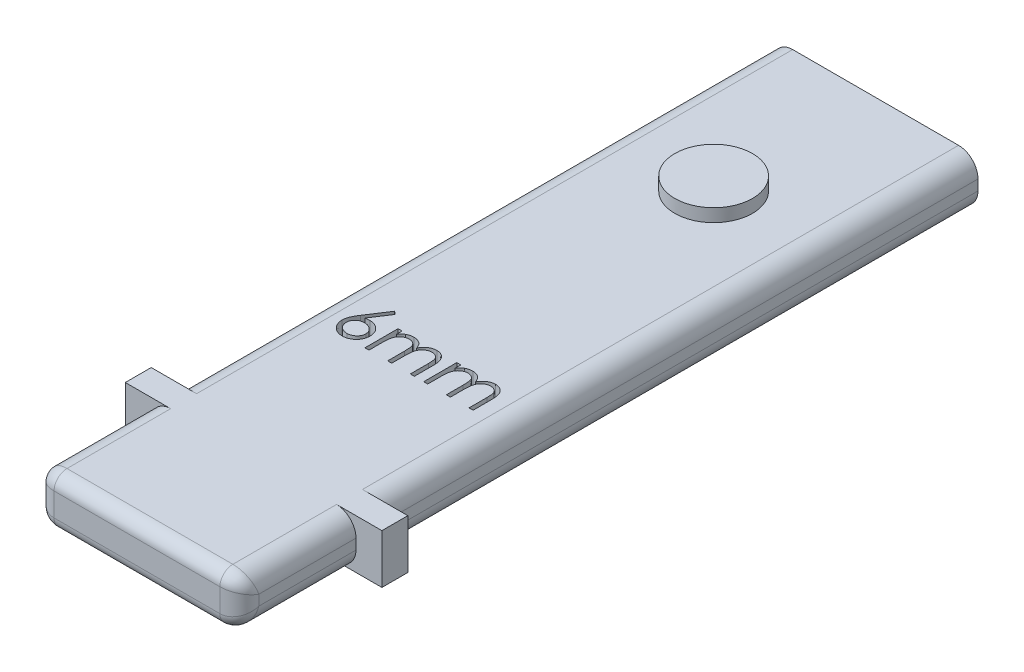
SolidWorks part; units mm, degrees
ref_plane "Front Plane" through (0, 0, 0) normal (0, 0, 1) x (1, 0, 0)
ref_plane "Top Plane" through (0, 0, 0) normal (0, 1, 0) x (1, 0, 0)
ref_plane "Right Plane" through (0, 0, 0) normal (1, 0, 0) x (0, 0, -1)
sketch "Sketch2" plane through (0, 0, 0) normal (0, 1, 0) x (1, 0, 0)
  line L1 (0, 0) -> (15.8, 0)
  line L2 (0, 0) -> (0, 57)
  line L3 (0, 57) -> (15.8, 57)
  line L4 (15.8, 0) -> (15.8, 57)
  dimension "D1" = 57
  dimension "D2" = 15.8
extrude "Boss-Extrude1" add sketch "Sketch2" along normal blind 3.8
fillet "Fillet3" radius 1 2 edges at (7.9, 0, 0) (7.9, 3.8, 0)
sketch "Sketch5" plane through (0, 3.8, 0) normal (0, 1, 0) x (1, 0, 0)
  line L0 (15.8, 57) -> (0, 57) construction
  circle A0 centre (7.9, 44.5) radius 3
  point P4 (7.9, 57)
  dimension "D1" = 6
  dimension "D2" = 12.5
extrude "Boss-Extrude4" add sketch "Sketch5" along normal blind 1
sketch "Sketch6" plane through (15.8, 0, 0) normal (1, 0, 0) x (0, 0, -1)
  line L0 (9, 3.8) -> (9, 0)
  line L1 (1, 3.8) -> (57, 3.8) construction
  line L2 (1, 0) -> (57, 0) construction
  line L3 (9, 0) -> (11, 0)
  line L4 (11, 0) -> (11, 3.8)
  line L5 (11, 3.8) -> (9, 3.8)
  line L6 (0, 2.8) -> (0, 1) construction
  dimension "D1" = 9
  dimension "D2" = 2
extrude "Boss-Extrude5" add sketch "Sketch6" along normal blind 2
sketch "Sketch7" plane through (0, 0, 0) normal (-1, 0, 0) x (0, 0, 1)
  line L0 (-57, 0) -> (-1, 0) construction
  line L1 (-9, 0) -> (-11, 0)
  line L2 (-9, 0) -> (-9, 3.8)
  line L3 (-9, 3.8) -> (-11, 3.8)
  line L4 (-11, 0) -> (-11, 3.8)
  line L5 (-57, 3.8) -> (-1, 3.8) construction
  line L6 (0, 2.8) -> (0, 1) construction
  dimension "D1" = 9
  dimension "D2" = 2
extrude "Boss-Extrude6" add sketch "Sketch7" along normal blind 2
fillet "Fillet4" radius 1.5 14 edges at (0, 0.2929, -0.2929) (0, 1.9, 0) (0, 3.5071, -0.2929) (15.8, 0.2929, -0.2929) (15.8, 1.9, 0) (15.8, 3.5071, -0.2929) (0, 0, -34) (0, 0, -5) (0, 3.8, -5) (0, 3.8, -34) (15.8, 0, -34) (15.8, 3.8, -34) (15.8, 0, -5) (15.8, 3.8, -5)
sketch "Sketch9" plane through (0, 3.8, 0) normal (0, 1, 0) x (1, 0, 0)
  text T0 "6mm\r\n"
extrude "Cut-Extrude1" cut sketch "Sketch9" against normal blind 5
